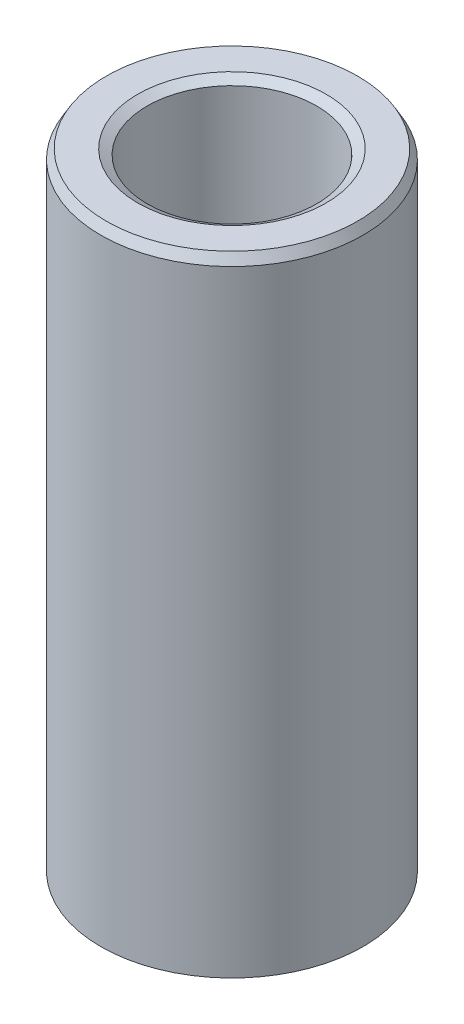
SolidWorks part; units mm, degrees
ref_plane "Front Plane" through (0, 0, 0) normal (0, 0, 1) x (1, 0, 0)
ref_plane "Top Plane" through (0, 0, 0) normal (0, 1, 0) x (1, 0, 0)
ref_plane "Right Plane" through (0, 0, 0) normal (1, 0, 0) x (0, 0, -1)
sketch "Sketch1" plane through (0, 0, 0) normal (0, 1, 0) x (1, 0, 0)
  circle A0 centre (0, 0) radius 32.5
  dimension "SLEEVE_OD" = 65
extrude "Boss-Extrude1" add sketch "Sketch1" along normal blind 156.3791
sketch "Sketch2" plane through (0, 0, 0) normal (0, 1, 0) x (1, 0, 0)
  circle A0 centre (0, 0) radius 21.0165
  dimension "BORE_D" = 42.033
extrude "Cut-Extrude1" cut sketch "Sketch2" along normal through all
chamfer "Chamfer1" distance 2.339 angle 30 4 edges at (0, 156.3791, 21.0165) (0, 0, 21.0165) (0, 0, 32.5) (0, 156.3791, 32.5) first distance on face at (0, 156.3791, 21.0165) first distance on face at (0, 0, 21.0165) first distance on face at (0, 156.3791, 32.5)
